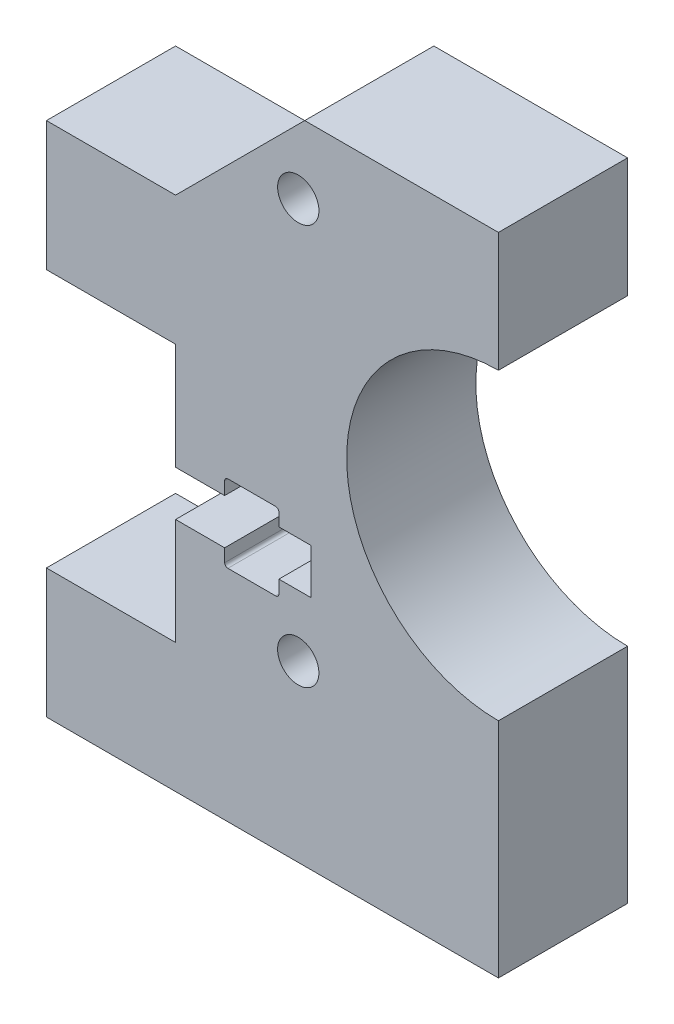
SolidWorks part; units mm, degrees
ref_plane "Front Plane" through (0, 0, 0) normal (0, 0, 1) x (1, 0, 0)
ref_plane "Top Plane" through (0, 0, 0) normal (0, 1, 0) x (1, 0, 0)
ref_plane "Right Plane" through (0, 0, 0) normal (1, 0, 0) x (0, 0, -1)
sketch "Sketch1" plane through (0, 0, 0) normal (0, 0, 1) x (1, 0, 0)
  line L0 (0, 0) -> (0, -60) construction
  line L1 (-10, -45) -> (0, -45) construction
  line L2 (25, -60) -> (25, 0) construction
  line L3 (25, 0) -> (0, 0) construction
  line L4 (0, 0) -> (0, -10)
  line L5 (0, -10) -> (-10, -10)
  line L6 (-10, -10) -> (-10, -20)
  line L7 (-10, -20) -> (0, -20)
  line L8 (0, -20) -> (0, -40)
  line L9 (25, -60) -> (0, -60) construction
  line L10 (0, -60) -> (25, -60)
  line L11 (-10, -40) -> (0, -40)
  line L12 (-10, -50) -> (-10, -40)
  line L13 (0, -50) -> (-10, -50)
  line L14 (25, -60) -> (25, 0)
  line L15 (0, 0) -> (25, 0)
  line L16 (0, -60) -> (0, -50)
  line L17 (-10, -15) -> (0, -15) construction
  line L18 (0, -30) -> (25, -30) construction
  dimension "D1" = 10
  dimension "D6" = 25
  dimension "D2" = 30
extrude "Boss-Extrude1" add sketch "Sketch1" along normal blind 10
sketch "Sketch2" plane through (0, 0, 10) normal (0, 0, 1) x (1, 0, 0)
  line L0 (25, -21) -> (0, -21) construction
  line L1 (25, -60) -> (25, 0) construction
  line L2 (0, -20) -> (0, -40) construction
  line L3 (25, -21) -> (9.5, -5.5) construction
  line L4 (25, -21) -> (9.5, -36.5) construction
  circle A0 centre (25, -21) radius 11.75
  circle A1 centre (9.5, -5.5) radius 1.6
  circle A2 centre (9.5, -36.5) radius 1.6
  point P6 (0, -30)
  dimension "D2" = 23.5
  dimension "D5" = 3.2
  dimension "D1" = 9
  dimension "D3" = 45
  dimension "D4" = 15.5
extrude "motor" cut sketch "Sketch2" against normal through all
sketch "Sketch3" plane through (0, 0, 10) normal (0, 0, 1) x (1, 0, 0)
  line L0 (0, -30) -> (10.5, -30) construction
  line L1 (0, -20) -> (0, -40) construction
  line L2 (10.5, -31.75) -> (10.5, -28.25) construction
  line L3 (10.5, -28.25) -> (0, -28.25) construction
  line L4 (0, -31.75) -> (0, -28.25)
  line L5 (0, -28.25) -> (3.8, -28.25)
  line L6 (3.8, -28.25) -> (3.8, -27.25)
  line L7 (4.05, -27) -> (7.75, -27)
  line L8 (8, -27.25) -> (8, -28.25)
  line L9 (8, -28.25) -> (10.5, -28.25)
  line L10 (10.5, -28.25) -> (10.5, -31.75)
  line L11 (10.5, -31.75) -> (0, -31.75) construction
  line L12 (8, -31.75) -> (10.5, -31.75)
  line L13 (8, -32.75) -> (8, -31.75)
  line L14 (4.05, -33) -> (7.75, -33)
  line L15 (3.8, -31.75) -> (3.8, -32.75)
  line L16 (0, -31.75) -> (3.8, -31.75)
  arc A0 (4.05, -33) -> (3.8, -32.75) centre (4.05, -32.75) cw
  arc A1 (8, -32.75) -> (7.75, -33) centre (7.75, -32.75) cw
  arc A2 (7.75, -27) -> (8, -27.25) centre (7.75, -27.25) cw
  arc A3 (3.8, -27.25) -> (4.05, -27) centre (4.05, -27.25) cw
  point P18 (3.8, -33)
  point P21 (8, -33)
  point P24 (8, -27)
  point P27 (3.8, -27)
  dimension "D6" = 0.25
  dimension "D1" = 1.75
  dimension "D2" = 8
  dimension "D3" = 10.5
  dimension "D4" = 3
  dimension "D5" = 4.2
extrude "screw" cut sketch "Sketch3" against normal through all
sketch "Sketch4" plane through (0, 0, 10) normal (0, 0, 1) x (1, 0, 0)
  line L0 (0, -50) -> (25, -50)
  line L1 (25, -60) -> (25, -32.75) construction
  line L2 (25, -50) -> (25, -60)
  line L3 (25, -60) -> (0, -60)
  line L4 (0, -60) -> (0, -50)
  line L5 (0, -10) -> (10, 0)
  line L6 (25, 0) -> (0, 0) construction
  line L7 (10, 0) -> (0, 0)
  line L8 (0, 0) -> (0, -10)
  dimension "D1" = 45
extrude "Cut-Extrude3" cut sketch "Sketch4" against normal through all
equation "\"X-ROD-SPACING\"=45"
equation "\"Y-ROD-SPACING\"=75"
equation "\"Z-ROD-SPACING\"=17.5"
equation "\"Y-BED-OFFSET\"=2"
equation "\"Y-BED-ROD-INSET\"=3.5"
equation "\"T-SLOT-NUT-FILLET-RADIUS\"=0.25"
equation "\"T-SLOT-SCREW-SHAFT-RADIUS\"=1.75"
equation "\"T-SLOT-SCREW-SHAFT-CUTOUT-LENGTH\"=10.5"
equation "\"T-SLOT-NUT-DEPTH\"=4.2"
equation "\"T-SLOT-NUT-WIDTH\"=3"
equation "\"T-SLOT-NUT-END-DISTANCE\"=8"
equation "\"ACRYLIC-THICKNESS\"=10"
equation "\"ACRYLIC-THICKNESS2\"=4.5"
equation "\"ACRYLIC-TAB-CUTOUT-SIZE\"=\"ACRYLIC-THICKNESS\"+\"ACRYLIC-TAB-TOLERANCE\"*2"
equation "\"ACRYLIC-TAB-WIDTH\"=\"ACRYLIC-THICKNESS\""
equation "\"ACRYLIC-M3-HOLE\"=3.2"
equation "\"SMOOTHROD-CAP-SCREW-DISTANCE\"=20"
equation "\"FRAME-WIDTH-INNER\"=370"
equation "\"NEMA17-HOLE-SPACING\"=31"
equation "\"NEMA17-CENTRAL-CUTOUT\"=22.5"
equation "\"Z-BRACKET-REACH\"=55"
equation "\"TOP-BRACKET-SPACING\"=40"
equation "\"SMOOTHROD-X-LENGTH\"=350"
equation "\"SMOOTHROD-Y-LENGTH\"=350"
equation "\"SMOOTHROD-Z-LENGTH\"=350"
equation "\"SMOOTHROD-TIGHTENING-HEADROOM\"=1"
equation "\"LEADSCREW-Z-LENGTH\"=300"
equation "\"SCREW-LENGTH-FRAME\"=\"ACRYLIC-THICKNESS\" + 10"
equation "\"SCREW-HEAD-RADIUS\"=6"
equation "\"PRINTED-X-SMOOTHROD-DIAMETER\"=8.2"
equation "\"PRINTED-X-SMOOTHROD-CUTOUT\"=10"
equation "\"PRINTED-X-BASE-HEIGHT\"=10"
equation "\"PRINTED-LM8UU-CUTOUT-SIZE\"=15.25"
equation "\"PRINTED-LM8UU-CUTOUT-LENGTH\"=24.5"
equation "\"PRINTED-X-IDLER-HEIGHT\"=16"
equation "\"PSU-MOUNTING-WIDTH\"=95"
equation "\"PSU-MOUNTING-HEIGHT\"=177"
equation "\"D1@Sketch1\"=10"
equation "\"D3@Sketch1\"=10"
equation "\"D1@Boss-Extrude1\"=\"ACRYLIC-THICKNESS\""
equation "\"D2@Sketch2\"=\"NEMA17-CENTRAL-CUTOUT\"+1"
equation "\"D4@Sketch2\"=\"NEMA17-HOLE-SPACING\"/2"
equation "\"D5@Sketch2\"=\"ACRYLIC-M3-HOLE\""
equation "\"D1@Sketch3\"=\"T-SLOT-SCREW-SHAFT-RADIUS\""
equation "\"D3@Sketch3\"=\"T-SLOT-SCREW-SHAFT-CUTOUT-LENGTH\""
equation "\"D4@Sketch3\"=\"T-SLOT-NUT-WIDTH\""
equation "\"D2@Sketch3\"=\"T-SLOT-NUT-END-DISTANCE\""
equation "\"D5@Sketch3\"=\"T-SLOT-NUT-DEPTH\""
equation "\"D6@Sketch3\"=\"T-SLOT-NUT-FILLET-RADIUS\""
